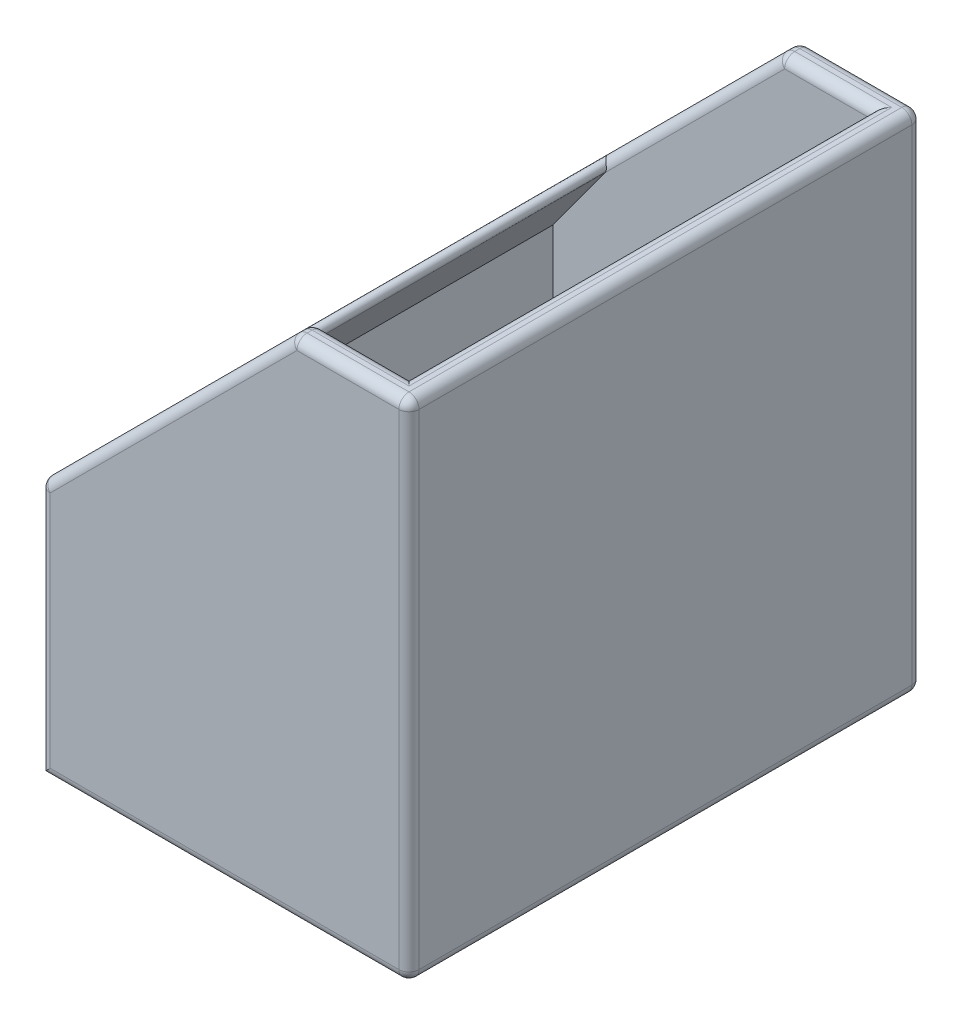
SolidWorks part; units mm, degrees
ref_plane "Front" through (0, 0, 0) normal (0, 0, 1) x (1, 0, 0)
ref_plane "Top" through (0, 0, 0) normal (0, 1, 0) x (1, 0, 0)
ref_plane "Right" through (0, 0, 0) normal (1, 0, 0) x (0, 0, -1)
sketch "Sketch1" plane through (0, 0, 0) normal (0, 1, 0) x (1, 0, 0)
  line L1 (-7.3, 10.15) -> (7.3, 10.15)
  line L2 (-7.3, 10.15) -> (-7.3, -10.15)
  line L3 (-7.3, -10.15) -> (7.3, -10.15)
  line L4 (7.3, 10.15) -> (7.3, -10.15)
  point P4 (0, 10.15)
  point P6 (-7.3, 0)
  dimension "D1" = 14.6
  dimension "D2" = 20.3
extrude "Extrude1" add sketch "Sketch1" along normal blind 20
sketch "Sketch4" plane through (0, 0, 0) normal (0, 0, 1) x (1, 0, 0)
  line L0 (-7.3, 20) -> (0, 20)
  line L3 (-7.3, 20) -> (7.3, 20) construction
  line L4 (-7.3, 20) -> (-7.3, 10)
  line L5 (-7.3, 20) -> (-7.3, 0) construction
  line L6 (-7.3, 10) -> (0, 20)
  line L8 (0, 20) -> (-5.8822, 11.9421)
extrude "Extrude3" cut sketch "Sketch4" against normal through all both and the other way through all contours L4 L6 L0 region at (-4.8667, 16.6667, 0)
sketch "Sketch5" plane through (0, 0, 0) normal (0, -1, 0) x (1, 0, 0)
  line L0 (-7.3, -10.15) -> (-7.3, 10.15) construction
  circle A0 centre (-7.3, 0) radius 0.5
  dimension "D1" = 1
extrude "Extrude4" add sketch "Sketch5" against normal blind 5
shell "Shell1" thickness 1 removed face at (-2.5167, 0, 0) removed face at (3.65, 20, 0)
sketch "Sketch7" plane through (0, 0, 0) normal (0, 0, 1) x (1, 0, 0)
  line L0 (2.7, 20) -> (-7.3, 10)
  line L1 (0, 20) -> (7.3, 20) construction
  line L2 (-7.3, 10) -> (0, 20) construction
  line L3 (2.7, 20) -> (0, 20)
  line L4 (0, 20) -> (-7.3, 10)
  dimension "D3" = 45
extrude "Extrude6" cut sketch "Sketch7" against normal through all both and the other way through all
sketch "Sketch9" plane through (0, 0, 0) normal (0, 0, 1) x (1, 0, 0)
  line L0 (-7.3, 0) -> (-7.8, 1.2)
  line L1 (-7.8, 5) -> (-7.8, 0) construction
  line L2 (-7.3, 0) -> (-7.8, 0)
  line L3 (-7.8, 0) -> (-7.8, 1.2)
  dimension "D1" = 1.2
extrude "Extrude7" cut sketch "Sketch9" against normal through all both and the other way through all
fillet "Fillet2" radius 0.2 1 edges at (-2.7144, 14.5856, 0)
fillet "Fillet3" radius 0.4 20 edges at (4.5, 20, 9.15) (6.3, 20, 0) (4.5, 20, -9.15) (2.7, 20, -9.65) (2.7, 20, 9.65) (0, 0, -10.15) (5, 20, -10.15) (-2.3, 15, -10.15) (-7.3, 5, -10.15) (7.3, 20, 0) (7.3, 10, -10.15) (7.3, 0, 0) (7.3, 10, 10.15) (0, 0, 10.15) (-7.3, 5, 10.15) (-2.3, 15, 10.15) (5, 20, 10.15) (-0.9188, 16.3812, -9.15) (-0.9188, 16.3812, 9.15) (-7.3, 10, 0)
